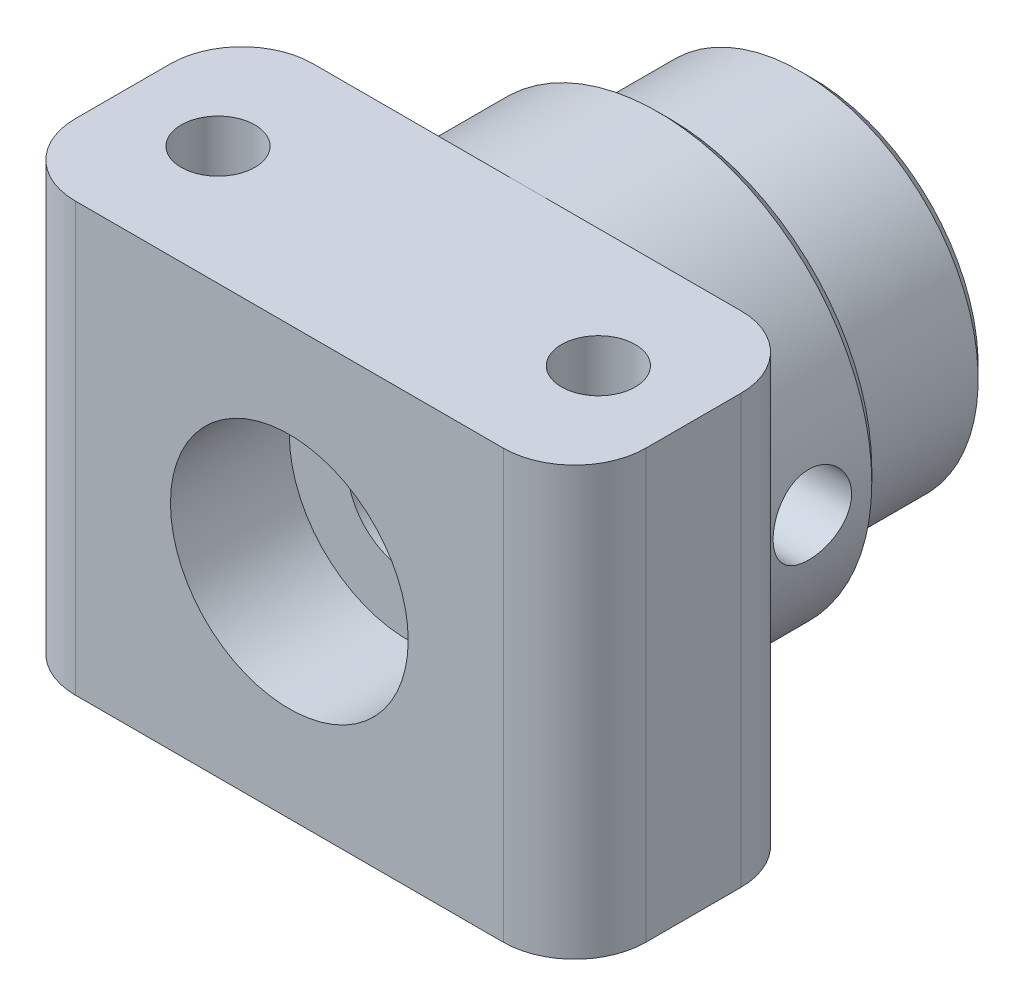
SolidWorks part; units mm, degrees
material "6061 Alloy"
ref_plane "前视基准面" through (0, 0, 0) normal (0, 0, 1) x (1, 0, 0)
ref_plane "上视基准面" through (0, 0, 0) normal (0, 1, 0) x (1, 0, 0)
ref_plane "右视基准面" through (0, 0, 0) normal (1, 0, 0) x (0, 0, -1)
sketch "草图1" plane through (0, 0, 0) normal (0, 0, 1) x (1, 0, 0)
  line L1 (-12, 9) -> (12, 9)
  line L2 (-12, 9) -> (-12, -9)
  line L3 (-12, -9) -> (12, -9)
  line L4 (12, 9) -> (12, -9)
  line L5 (-12, 9) -> (12, -9) construction
  line L6 (-12, -9) -> (12, 9) construction
  point P0 (0, 0)
  dimension "D1" = 24
  dimension "D2" = 18
extrude "凸台-拉伸1" add sketch "草图1" along normal blind 10
sketch "草图2" plane through (0, 0, 0) normal (0, 0, 1) x (1, 0, 0)
  circle A0 centre (0, 0) radius 5.275
  circle A1 centre (0, 0) radius 9
  dimension "D1" = 10.55
  dimension "D2" = 18
extrude "凸台-拉伸2" add sketch "草图2" against normal blind 6
sketch "草图3" plane through (0, 0, 0) normal (0, 0, -1) x (-1, 0, 0)
  circle A0 centre (0, 0) radius 2.55
  dimension "D1" = 5.1
extrude "切除-拉伸1" cut sketch "草图3" against normal blind 41
sketch "草图4" plane through (0, 9, 0) normal (0, 1, 0) x (1, 0, 0)
  line L0 (-12, -5) -> (12, -5) construction
  line L1 (-12, -10) -> (-12, 0) construction
  line L2 (12, -10) -> (12, 0) construction
  circle A0 centre (-8, -5) radius 1.55
  circle A1 centre (8, -5) radius 1.55
  dimension "D1" = 3.1
  dimension "D2" = 3.1
  dimension "D4" = 4
  dimension "D3" = 4
extrude "切除-拉伸2" cut sketch "草图4" against normal blind 37.0135
ref_plane "基准面1" through (9, 0, 0) normal (1, 0, 0) x (0, 0, -1)
sketch "草图7" plane through (9, 0, 0) normal (1, 0, 0) x (0, 0, -1)
  line L0 (0, 0) -> (3, 0) construction
  dimension "D1" = 3
hole_wizard "M4 Tapped Hole1" positions "草图8" profile "草图9" tap size "M4" standard "GB"
sketch "草图8" plane through (9, 0, 0) normal (1, 0, 0) x (0, 0, -1)
  point P0 (3, 0)
sketch "草图9" plane through (9, 0, -3) normal (0, 1, 0) x (0, 0, -1)
  line L0 (0, 0) -> (0, 24.4914)
  line L1 (0, 24.4914) -> (1.65, 23.5)
  line L2 (1.65, 23.5) -> (1.65, 0)
  line L5 (1.65, 0) -> (0, 0)
  line L10 (0, 24.4914) -> (-1.65, 23.5) construction
  line L11 (0, -6.35) -> (0, 107.95) construction
  dimension "螺纹孔钻头直径" = 3.3
  dimension "螺纹孔钻头深度" = 23.5
  dimension "导头角度" = 118
cosmetic thread "孔螺蚊线1" parameters "D1"=18, "D2"=4
ref_plane "Plane1" through (0, 0, 0) normal (0.7071, -0.7071, 0) x (-0.7071, -0.7071, 0)
mirror "Mirror1" [suppressed] about plane through (0, 0, 0) normal (0.7071, -0.7071, 0)
sketch "Sketch2" plane through (0, 0, -6) normal (0, 0, -1) x (-1, 0, 0)
  circle A0 centre (0, 0) radius 7.475
  circle A1 centre (0, 0) radius 5.275
  dimension "D1" = 10.55
  dimension "D2" = 14.95
extrude "Boss-Extrude1" add sketch "Sketch2" along normal blind 6
chamfer "Chamfer1" distance 0.5 angle 45 2 edges at (-7.475, 0, -12) (9, 0, -6)
sketch "Sketch3" plane through (0, 0, 10) normal (0, 0, 1) x (1, 0, 0)
  circle A0 centre (0, 0) radius 5
  dimension "D1" = 10
extrude "Cut-Extrude1" cut sketch "Sketch3" against normal blind 5
fillet "Fillet1" radius 3 4 edges at (12, 0, 10) (12, 0, 0) (-12, 0, 10) (-12, 0, 0)
